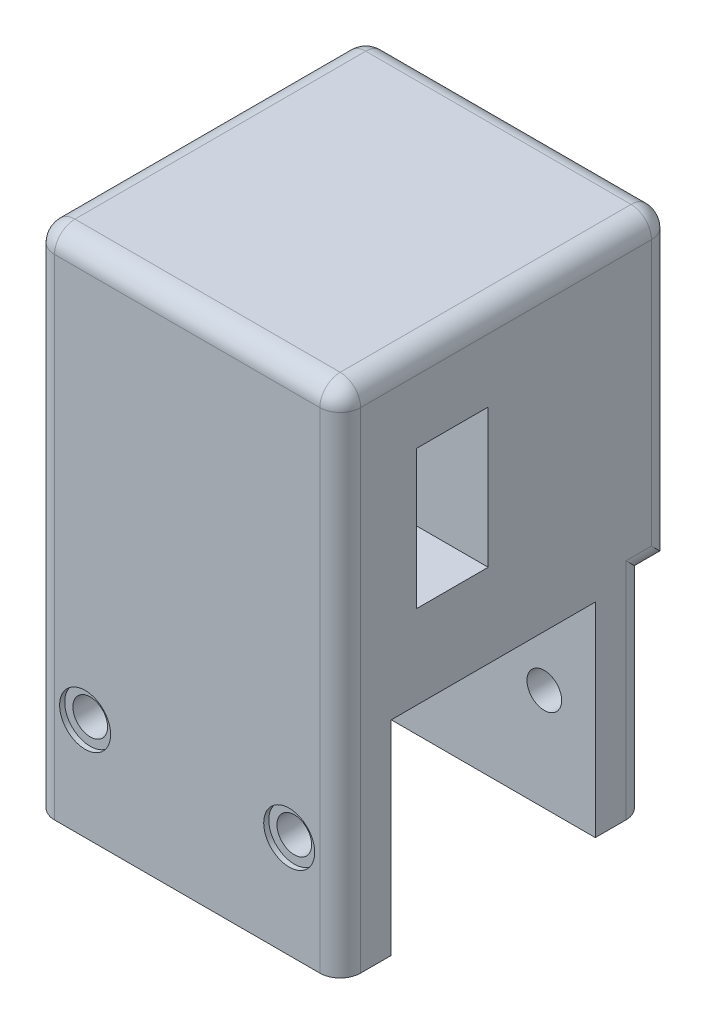
SolidWorks part; units mm, degrees
material "ABS"
ref_plane "Front Plane" through (0, 0, 0) normal (0, 0, 1) x (1, 0, 0)
ref_plane "Top Plane" through (0, 0, 0) normal (0, 1, 0) x (1, 0, 0)
ref_plane "Right Plane" through (0, 0, 0) normal (1, 0, 0) x (0, 0, -1)
sketch "Sketch1" plane through (0, 0, 0) normal (0, 0, 1) x (1, 0, 0)
  line L1 (15, -25) -> (-15, -25)
  line L2 (15, -25) -> (15, 25)
  line L3 (15, 25) -> (-15, 25)
  line L4 (-15, -25) -> (-15, 25)
  line L5 (15, -25) -> (-15, 25) construction
  line L6 (15, 25) -> (-15, -25) construction
  point P0 (0, 0)
  dimension "D1" = 30
  dimension "D2" = 50
extrude "Boss-Extrude1" add sketch "Sketch1" along normal mid plane 30
sketch "Sketch6" plane through (0, 0, -15) normal (0, 0, -1) x (-1, 0, 0)
  line L0 (-15, -25) -> (-15, 25) construction
  line L1 (15, 25) -> (-15, 25)
  line L2 (15, 25) -> (15, -5)
  line L3 (15, -5) -> (-15, -5)
  line L4 (-15, 25) -> (-15, -5)
  dimension "D1" = 30
extrude "Boss-Extrude2" add sketch "Sketch6" along normal blind 2.5
sketch "Sketch2" plane through (0, -25, 0) normal (0, -1, 0) x (1, 0, 0)
  line L0 (15, 15) -> (15, -15) construction
  line L1 (-15, -10) -> (15, -10)
  line L2 (-15, -10) -> (-15, 10)
  line L3 (-15, 10) -> (15, 10)
  line L4 (15, -10) -> (15, 10)
  line L5 (-15, -10) -> (15, 10) construction
  line L6 (-15, 10) -> (15, -10) construction
  point P0 (0, 0)
  dimension "D1" = 20
extrude "Cut-Extrude1" cut sketch "Sketch2" against normal blind 20
sketch "Sketch3" plane through (0, 0, 10) normal (0, 0, -1) x (-1, 0, 0)
  line L0 (-15, -15) -> (-10, -15) construction
  line L1 (0, -5) -> (0, -25) construction
  line L4 (-15, -25) -> (15, -25)
  line L5 (15, -25) -> (15, -5)
  line L6 (15, -5) -> (-15, -5)
  line L7 (-15, -5) -> (-15, -25)
  line L8 (-15, -25) -> (15, -25)
  line L9 (15, -25) -> (15, -5)
  line L10 (15, -5) -> (-15, -5)
  line L11 (-15, -5) -> (-15, -25)
  circle A0 centre (-10, -15) radius 1.7
  circle A1 centre (10, -15) radius 1.7
  circle A2 centre (-10, -15) radius 2.5
  dimension "D3" = 3.4
  dimension "D4" = 5
  dimension "D2" = 5
  dimension "D1" = 0
extrude "Cut-Extrude2" cut sketch "Sketch3" against normal through all and the other way through all contours A0 | A1
sketch "Sketch5" plane through (15, 0, 0) normal (1, 0, 0) x (0, 0, -1)
  line L1 (-0.5, 16.8) -> (-7.5, 16.8)
  line L2 (-0.5, 16.8) -> (-0.5, 3.2)
  line L3 (-0.5, 3.2) -> (-7.5, 3.2)
  line L4 (-7.5, 16.8) -> (-7.5, 3.2)
  line L5 (-0.5, 16.8) -> (-7.5, 3.2) construction
  line L6 (-0.5, 3.2) -> (-7.5, 16.8) construction
  point P0 (-4, 10)
  dimension "D1" = 10
  dimension "D2" = 4
  dimension "D3" = 13.6
  dimension "D4" = 7
extrude "Cut-Extrude5" cut sketch "Sketch5" against normal blind 22.8
extrude "Cut-Extrude8" cut sketch "Sketch3<4>" against normal blind 0.5 from offset 4.5 contours A2 offset against normal yes
sketch "Sketch3<4>" plane through (0, 0, 10) normal (0, 0, -1) x (-1, 0, 0) same geometry as "Sketch3"
mirror "Mirror3" about plane through (0, 0, 0) normal (1, 0, 0) of "Cut-Extrude8"
mirror "Mirror4" about plane through (0, 0, 0) normal (0, 0, 1) of "Mirror3"
fillet "Fillet1" radius 2 12 edges at (0, 25, 15) (-15, 25, -1.25) (0, 25, -17.5) (15, 25, -1.25) (-15, -15, -15) (-15, -5, -16.25) (-15, 10, -17.5) (15, 10, -17.5) (15, -5, -16.25) (15, -15, -15) (-15, 0, 15) (15, 0, 15)
sketch "Sketch7" plane through (0, 0, -17.5) normal (0, 0, -1) x (-1, 0, 0)
  line L0 (-13, 25) -> (13, 25) construction
  circle A0 centre (0, 10) radius 4.5
  circle A1 centre (0, 10) radius 12
  point P5 (0, 0)
  dimension "D2" = 24
  dimension "D3" = 9
  dimension "D1" = 15
extrude "Cut-Extrude9" cut sketch "Sketch7" against normal blind 12 contours A0 | A1 A0 region at (0, 10, -17.5) region at (11.6606, 10, -17.5)
extrude "Cut-Extrude10" cut sketch "Sketch7<4>" against normal up to next contours A0 region at (0, 10, -17.5)
sketch "Sketch7<4>" plane through (0, 0, -17.5) normal (0, 0, -1) x (-1, 0, 0) same geometry as "Sketch7"
